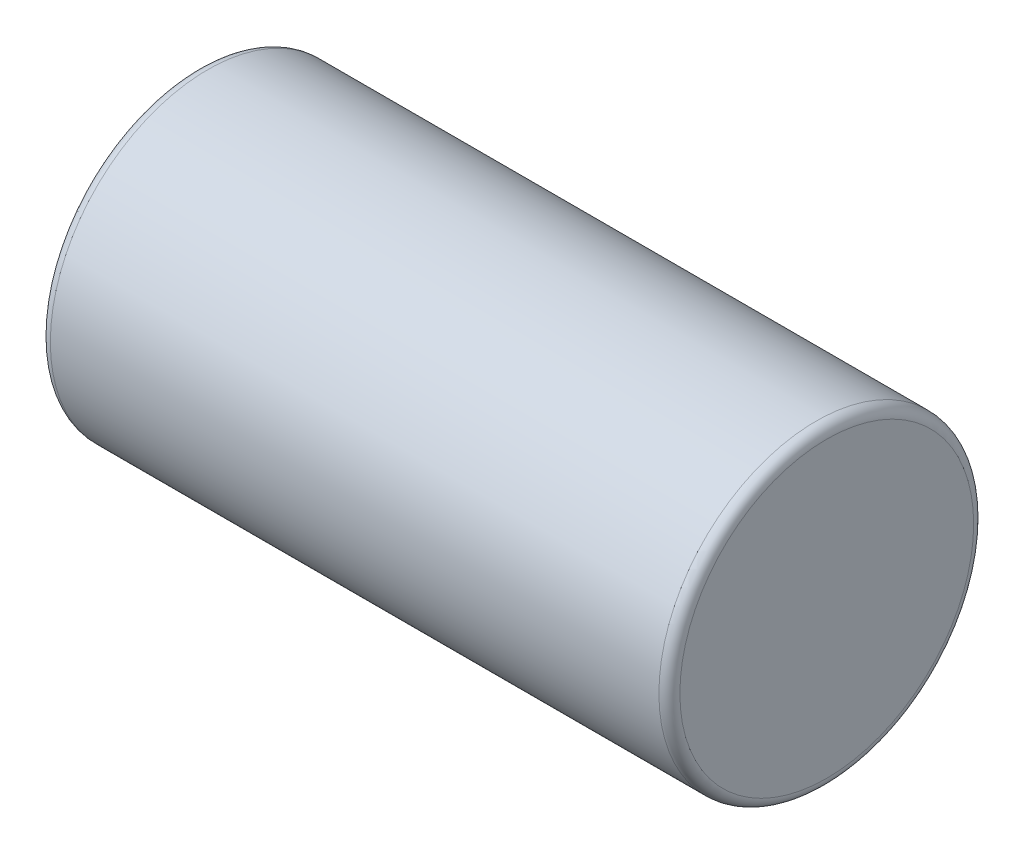
SolidWorks part; units mm, degrees
ref_plane "Front Plane" through (0, 0, 0) normal (0, 0, 1) x (1, 0, 0)
ref_plane "Top Plane" through (0, 0, 0) normal (0, 1, 0) x (1, 0, 0)
ref_plane "Right Plane" through (0, 0, 0) normal (1, 0, 0) x (0, 0, -1)
sketch "Sketch1" plane through (0, 0, 0) normal (1, 0, 0) x (0, 0, -1)
  circle A0 centre (0, 0) radius 1.5
  dimension "D1" = 3
extrude "Boss-Extrude1" add sketch "Sketch1" along normal mid plane 6
fillet "Fillet1" radius 0.1 2 edges at (-3, 0, -1.5) (3, 0, -1.5)
ref_axis "Axis1" through (0, 1.65, 0) along (0, -1, 0)
